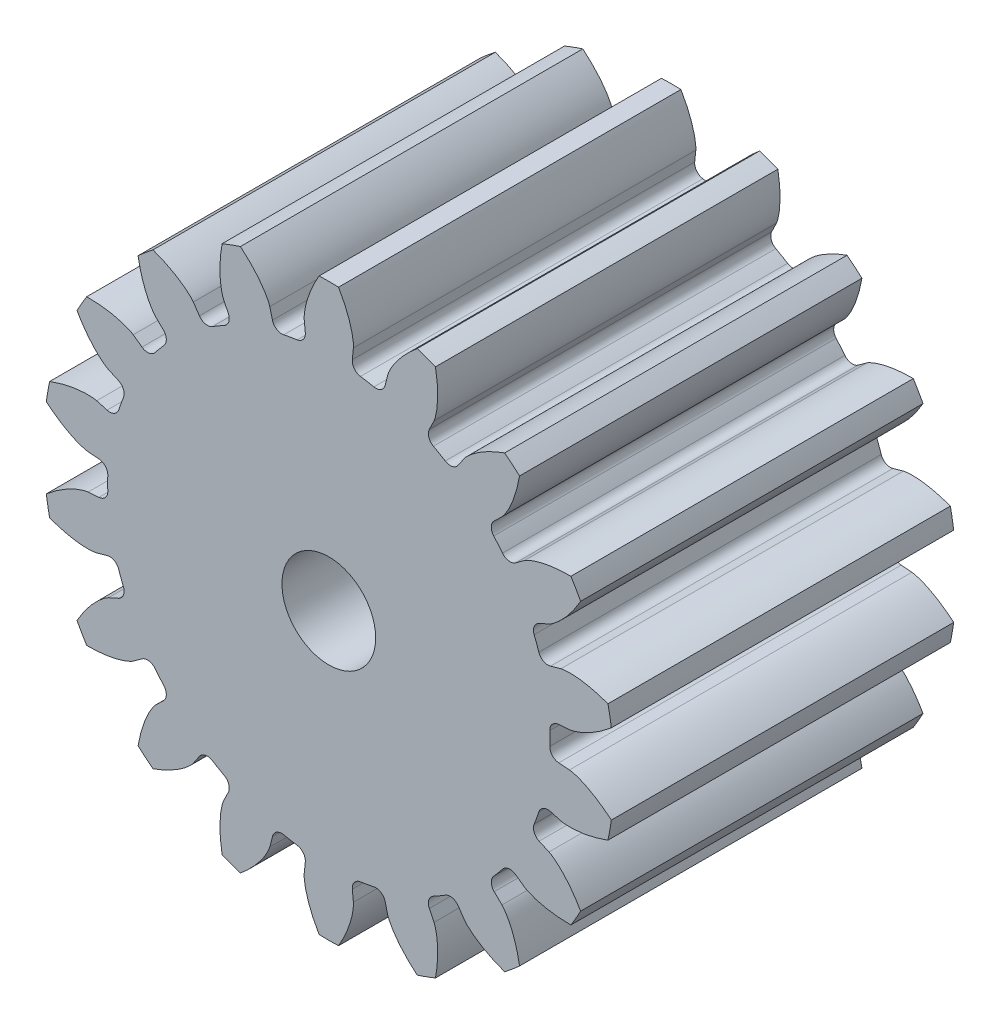
SolidWorks part; units mm, degrees
ref_plane "Front Plane" through (0, 0, 0) normal (0, 0, 1) x (1, 0, 0)
ref_plane "Top Plane" through (0, 0, 0) normal (0, 1, 0) x (1, 0, 0)
ref_plane "Right Plane" through (0, 0, 0) normal (1, 0, 0) x (0, 0, -1)
sketch "Sketch1" plane through (0, 0, 0) normal (0, 0, 1) x (1, 0, 0)
  line L0 (0, 0) -> (0, 9.525) construction
  line L1 (-3.0613, 10.6392) -> (3.0613, 8.4108) construction
  circle A0 centre (0, 0) radius 8.2021 construction
  circle A1 centre (0, 0) radius 10.5833 construction
  circle A2 centre (0, 0) radius 9.525 construction
  circle A3 centre (0, 0) radius 8.9506 construction
  circle A4 centre (0, 0) radius 2.3813 construction
  circle A5 centre (0, 0) radius 6.858 construction
  point P8 (304.8, 0)
  point P13 (228.6, 0)
  dimension "OD | Outside Diameter" = 21.1667
  dimension "Root Diameter" = 16.4042
  dimension "Gear Pitch Diameter" = 19.05
  dimension "Base Diameter" = 17.9011
  dimension "For Shaft Diameter" = 4.7625
  dimension "Hub Diameter" = 13.716
  dimension "Pressure Angle" = 20
  dimension "Number of Teeth" = 457.2
  dimension "Gear Pitch | Diametral Pitch" = 609.6
sketch "Sketch2" plane through (0, 0, 0) normal (1, 0, 0) x (0, 0, -1)
  line L0 (-6.35, 0) -> (6.35, 0) construction
  line L1 (-6.35, 10.5833) -> (6.35, 10.5833) construction
  point P2 (0, 10.5833)
  point P4 (0, 0)
  point P6 (0, 10.5833)
  dimension "Overall Width" = 12.7
  dimension "Hub Width" = 6.35
  dimension "Face Width" = 6.35
sketch "Sketch3" plane through (0, 0, 0) normal (0, 0, 1) x (1, 0, 0)
  circle A0 centre (0, 0) radius 10.5833
  circle A1 centre (0, 0) radius 10.5833 construction
extrude "Boss-Extrude1" add sketch "Sketch3" against normal blind 12.7
sketch "Sketch4" plane through (0, 0, 0) normal (0, 0, 1) x (1, 0, 0)
  line L0 (0, 0) -> (8.1806, 0.593) construction
  line L2 (0, 0) -> (8.1806, -0.593) construction
  line L4 (8.1806, 0.593) -> (8.9271, 0.6471)
  line L5 (8.9271, -0.6471) -> (8.1806, -0.593)
  arc A0 (8.1806, 0.593) -> (8.1806, -0.593) centre (0, 0) cw
  arc A3 (10.4791, 1.4815) -> (10.4791, -1.4815) centre (0, 0) cw
  circle A4 centre (0, 0) radius 10.5833 construction
  spline S0 degree 4 poles (8.9271, 0.6471) (8.9298, 0.6473) (8.9371, 0.6481) (8.951, 0.6499) (8.9735, 0.6535) (9.0022, 0.659) (9.039, 0.6671) (9.0823, 0.6779) (9.1296, 0.6912) (9.1807, 0.7071) (9.2315, 0.7243) (9.2819, 0.7426) (9.3319, 0.762) (9.3922, 0.7867) (9.464, 0.8182) (9.5473, 0.8575) (9.6409, 0.905) (9.7354, 0.9567) (9.8276, 1.0102) (9.9198, 1.0673) (10.0083, 1.1246) (10.0992, 1.1871) (10.1825, 1.2464) (10.2747, 1.3161) (10.3487, 1.3734) (10.4449, 1.4524) (10.5013, 1.5001) (10.5668, 1.5571) (10.5956, 1.5831) (10.6134, 1.599) knots 0 0 0 0 0 0.005377 0.015084 0.028532 0.04661 0.064855 0.092111 0.119476 0.146842 0.174209 0.201575 0.228941 0.256307 0.307035 0.361767 0.4165 0.471232 0.525964 0.580697 0.635429 0.690161 0.744894 0.799626 0.854358 0.909091 0.954545 1 1 1 1 1 construction
  spline S1 degree 4 poles (8.9271, 0.6471) (8.9298, 0.6473) (8.9371, 0.6481) (8.951, 0.6499) (8.9735, 0.6535) (9.0022, 0.659) (9.039, 0.6671) (9.0823, 0.6779) (9.1296, 0.6912) (9.1807, 0.7071) (9.2315, 0.7243) (9.2819, 0.7426) (9.3319, 0.762) (9.3922, 0.7867) (9.464, 0.8182) (9.5473, 0.8575) (9.6409, 0.905) (9.7354, 0.9567) (9.8276, 1.0102) (9.9198, 1.0673) (10.0083, 1.1246) (10.0992, 1.1871) (10.1825, 1.2464) (10.2747, 1.3161) (10.3487, 1.3734) (10.424, 1.4353) (10.4605, 1.4658) (10.4791, 1.4815) knots 0 0 0 0 0 0.005377 0.015084 0.028532 0.04661 0.064855 0.092111 0.119476 0.146842 0.174209 0.201575 0.228941 0.256307 0.307035 0.361767 0.4165 0.471232 0.525964 0.580697 0.635429 0.690161 0.744894 0.799626 0.854358 0.909091 0.909091 0.909091 0.909091 0.909091
  spline S2 degree 4 poles (8.9271, -0.6471) (8.9298, -0.6473) (8.9371, -0.6481) (8.951, -0.6499) (8.9735, -0.6535) (9.0022, -0.659) (9.039, -0.6671) (9.0823, -0.6779) (9.1296, -0.6912) (9.1807, -0.7071) (9.2315, -0.7243) (9.2819, -0.7426) (9.3319, -0.762) (9.3922, -0.7867) (9.464, -0.8182) (9.5473, -0.8575) (9.6409, -0.905) (9.7354, -0.9567) (9.8276, -1.0102) (9.9198, -1.0673) (10.0083, -1.1246) (10.0992, -1.1871) (10.1825, -1.2464) (10.2747, -1.3161) (10.3487, -1.3734) (10.4449, -1.4524) (10.5013, -1.5001) (10.5668, -1.5571) (10.5956, -1.5831) (10.6134, -1.599) knots 0 0 0 0 0 0.005377 0.015084 0.028532 0.04661 0.064855 0.092111 0.119476 0.146842 0.174209 0.201575 0.228941 0.256307 0.307035 0.361767 0.4165 0.471232 0.525964 0.580697 0.635429 0.690161 0.744894 0.799626 0.854358 0.909091 0.954545 1 1 1 1 1 construction
  spline S3 degree 4 poles (8.9271, -0.6471) (8.9298, -0.6473) (8.9371, -0.6481) (8.951, -0.6499) (8.9735, -0.6535) (9.0022, -0.659) (9.039, -0.6671) (9.0823, -0.6779) (9.1296, -0.6912) (9.1807, -0.7071) (9.2315, -0.7243) (9.2819, -0.7426) (9.3319, -0.762) (9.3922, -0.7867) (9.464, -0.8182) (9.5473, -0.8575) (9.6409, -0.905) (9.7354, -0.9567) (9.8276, -1.0102) (9.9198, -1.0673) (10.0083, -1.1246) (10.0992, -1.1871) (10.1825, -1.2464) (10.2747, -1.3161) (10.3487, -1.3734) (10.424, -1.4353) (10.4605, -1.4658) (10.4791, -1.4815) knots 0 0 0 0 0 0.005377 0.015084 0.028532 0.04661 0.064855 0.092111 0.119476 0.146842 0.174209 0.201575 0.228941 0.256307 0.307035 0.361767 0.4165 0.471232 0.525964 0.580697 0.635429 0.690161 0.744894 0.799626 0.854358 0.909091 0.909091 0.909091 0.909091 0.909091
  dimension "D1" = 16.4042
extrude "Cut-Extrude1" cut sketch "Sketch4" against normal through all both and the other way through all
fillet "Fillet1" radius 0.3551 2 edges at (8.1806, -0.593, -6.35) (8.1806, 0.593, -6.35)
pattern_circular "CirPattern1" count 18 over 360 about axis through (0, 0, 6.35) along (0, 0, -1) of "Cut-Extrude1", "Fillet1"
scale "Scale1" scale about centroid uniform scaling yes scale factor 1.9
sketch "Sketch6" plane through (0, 0, 5.715) normal (0, 0, 1) x (1, 0, 0)
  circle A0 centre (0, 0) radius 3.302
  dimension "D1" = 6.604
extrude "Cut-Extrude2" cut sketch "Sketch6" against normal blind 10.16
sketch "Sketch7" plane through (0, 0, -18.415) normal (0, 0, -1) x (-1, 0, 0)
  circle A0 centre (0, 0) radius 9.525
  dimension "D1" = 19.05
sketch "Sketch8" plane through (0, 0, -18.415) normal (0, 0, -1) x (-1, 0, 0)
  line L0 (0, 0) -> (0, 7.9242) construction
  line L1 (-8.1304, 0) -> (-9.7802, 2.8575)
  line L2 (-9.7802, 2.8575) -> (-13.0798, 2.8575)
  line L3 (-13.0798, 2.8575) -> (-14.7296, 0)
  line L4 (-14.7296, 0) -> (-13.0798, -2.8575)
  line L5 (-13.0798, -2.8575) -> (-9.7802, -2.8575)
  line L6 (-9.7802, -2.8575) -> (-8.1304, 0)
  line L7 (14.7296, 0.0217) -> (13.0798, 2.8792)
  line L8 (13.0798, 2.8792) -> (9.7802, 2.8792)
  line L9 (9.7802, 2.8792) -> (8.1304, 0.0217)
  line L10 (8.1304, 0.0217) -> (9.7802, -2.8358)
  line L11 (9.7802, -2.8358) -> (13.0798, -2.8358)
  line L12 (13.0798, -2.8358) -> (14.7296, 0.0217)
  circle A0 centre (-11.43, 0) radius 2.8575 construction
  circle A1 centre (11.43, 0.0217) radius 2.8575 construction
  dimension "D1" = 5.715
  dimension "D2" = 22.86
  dimension "D3" = 11.43
extrude "Cut-Extrude3" cut sketch "Sketch8" against normal blind 3.048
sketch "Sketch9" plane through (0, 0, -15.367) normal (0, 0, -1) x (-1, 0, 0)
  line L0 (0, 0) -> (0, 5.3987) construction
  circle A0 centre (-11.43, 0) radius 1.4605
  circle A1 centre (11.43, 0) radius 1.4605
  dimension "D1" = 22.86
  dimension "D3" = 2.921
  dimension "D2" = 11.43
extrude "Cut-Extrude4" cut sketch "Sketch9" against normal blind 10.16
equation "\"Root Diameter@Sketch1\"=\"Root Diameter\""
equation "\"OD | Outside Diameter@Sketch1\"=\"Outside Diameter\""
equation "\"D1@CirPattern1\"=\"Number of Teeth\""
equation "\"Diametral Pitch\"= 24"
equation "\"Number of Teeth\"= 18"
equation "\"Pressure Angle\"=20"
equation "\"Pitch Diameter\"= \"Number of Teeth\" / \"Diametral Pitch\""
equation "\"Base Diameter\"= \"Pitch Diameter\" * cos ( \"Pressure Angle\" )"
equation "\"Outside Diameter\"= ( \"Number of Teeth\" + 2 ) / \"Diametral Pitch\""
equation "\"Dedendum\"= 1.25 / \"Diametral Pitch\""
equation "\"Root Diameter\"= \"Pitch Diameter\" - ( 2 * \"Dedendum\" )"
equation "\"Pitch Angle\"= 360deg / \"Number of Teeth\""
equation "\"Alpha\"= sqr ( \"Pitch Diameter\" ^ 2 - \"Base Diameter\" ^ 2 ) / \"Base Diameter\" * 180 / PI - \"Pressure Angle\""
equation "\"Beta\"= ( \"Pitch Angle\" / 4 - \"Alpha\" )"
equation "\"Phi\"= sqr ( ( \"Outside Diameter\" / 2 ) ^ 2 - ( \"Base Diameter\" / 2 ) ^ 2 ) / ( \"Base Diameter\" / 2 )"
equation "\"Addendum\"= 1 / \"Diametral Pitch\""
equation "\"WorkingDepth\"= 2 / \"Diametral Pitch\""
equation "\"WholeDepth\"= 2.25 / \"Diametral Pitch\""
equation "\"Clearance\"= 0.25 / \"Diametral Pitch\""
equation "\"ToothThickness\"= ( pi * 2 ) / \"Diametral Pitch\""
equation "\"CircularPitch\"= pi / \"Diametral Pitch\""
equation "\"Number of Teeth@Sketch1\"=\"Number of Teeth\""
equation "\"Gear Pitch | Diametral Pitch@Sketch1\"=\"Diametral Pitch\""
equation "\"Pressure Angle@Sketch1\"=\"Pressure Angle\""
equation "\"Gear Pitch Diameter@Sketch1\"=\"Pitch Diameter\""
equation "\"Base Diameter@Sketch1\"=\"Base Diameter\""
equation "\"Fillet\"= \"Clearance\" * cos ( \"Pressure Angle\" ) * tan ( ( 90 + \"Pressure Angle\" ) / 2 )"
equation "\"D1@Fillet1\"=\"Fillet\""
equation "\"D1@Sketch4\"=if( \"Base Diameter\">\"Root Diameter\",\"Root Diameter\",\"Base Diameter\"-.00001)"
equation "\"D1@Fillet2\"=\"Fillet\""
